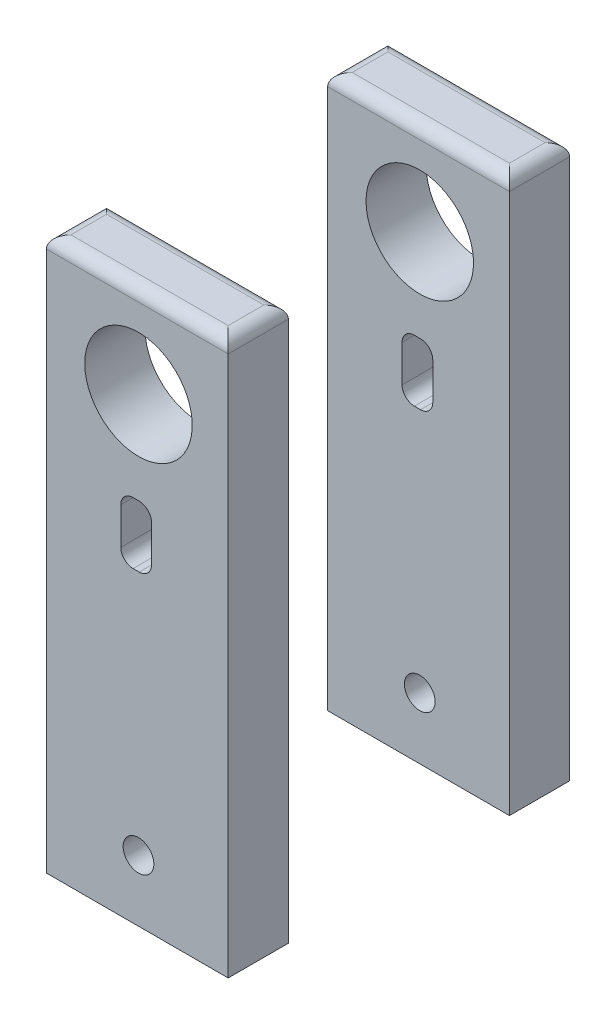
SolidWorks part; units mm, degrees
ref_plane "Front Plane" through (0, 0, 0) normal (0, 0, 1) x (1, 0, 0)
ref_plane "Top Plane" through (0, 0, 0) normal (0, 1, 0) x (1, 0, 0)
ref_plane "Right Plane" through (0, 0, 0) normal (1, 0, 0) x (0, 0, -1)
sketch "Sketch2" plane through (0, 0, 0) normal (0, 1, 0) x (1, 0, 0)
  line L0 (-19.05, 6.223) -> (18.542, 6.223)
  line L1 (0, 0) -> (12.6901, 0) construction
  line L2 (-19.05, -6.223) -> (18.542, -6.223)
  line L3 (-19.05, 6.223) -> (-19.05, -6.223)
  line L4 (18.542, 6.223) -> (18.542, -6.223)
  point P3 (-0.254, 6.223)
  dimension "D1" = 37.592
  dimension "D2" = 6.223
  dimension "D3" = 12.446
extrude "Boss-Extrude1" add sketch "Sketch2" along normal blind 114.3
ref_plane "Plane1" through (0, 0, 29.083) normal (0, 0, 1) x (1, 0, 0)
sketch "Sketch3" plane through (0, 0, -6.223) normal (0, 0, -1) x (-1, 0, 0)
  circle A0 centre (0, 12.7) radius 3.175
  dimension "D1" = 12.7
sketch "Sketch4" plane through (0, 0, -6.223) normal (0, 0, -1) x (-1, 0, 0)
  circle A0 centre (0, 95.25) radius 11.1125
  dimension "D1" = 95.25
  dimension "D2" = 22.225
extrude "Cut-Extrude1" cut sketch "Sketch3" against normal blind 12.7
extrude "Cut-Extrude2" cut sketch "Sketch4" against normal blind 12.7
sketch "Sketch5" plane through (0, 0, -6.223) normal (0, 0, -1) x (-1, 0, 0)
  line L0 (-2.6881, 76.2) -> (-2.6881, 63.5)
  line L1 (-2.6881, 76.2) -> (3.6619, 76.2)
  line L2 (-2.6881, 63.5) -> (3.6619, 63.5)
  line L3 (3.6619, 76.2) -> (3.6619, 63.5)
  line L4 (-2.6881, 76.2) -> (3.6619, 63.5) construction
  line L5 (-2.6881, 63.5) -> (3.6619, 76.2) construction
  line L6 (0.254, 0) -> (11.2164, 0) construction
  line L7 (-18.542, 0) -> (19.05, 0) construction
  point P1 (0.4869, 69.85)
  dimension "D1" = 12.7
  dimension "D2" = 6.35
  dimension "D3" = 63.5
extrude "Cut-Extrude3" cut sketch "Sketch5" against normal blind 12.7
mirror "Mirror7" about plane through (0, 0, 29.083) normal (0, 0, 1) of bodies 104
fillet "Fillet2" radius 2.54 4 edges at (2.6881, 76.2, 0) (-3.6619, 76.2, 0) (2.6881, 63.5, 0) (-3.6619, 63.5, 0)
fillet "Fillet3" radius 2.54 4 edges at (2.6881, 63.5, 58.166) (2.6881, 76.2, 58.166) (-3.6619, 76.2, 58.166) (-3.6619, 63.5, 58.166)
fillet "Fillet4" radius 2.54 4 edges at (18.542, 114.3, 0) (-0.254, 114.3, 6.223) (-19.05, 114.3, 0) (-0.254, 114.3, -6.223)
fillet "Fillet5" radius 2.54 4 edges at (-0.254, 114.3, 64.389) (-19.05, 114.3, 58.166) (-0.254, 114.3, 51.943) (18.542, 114.3, 58.166)
